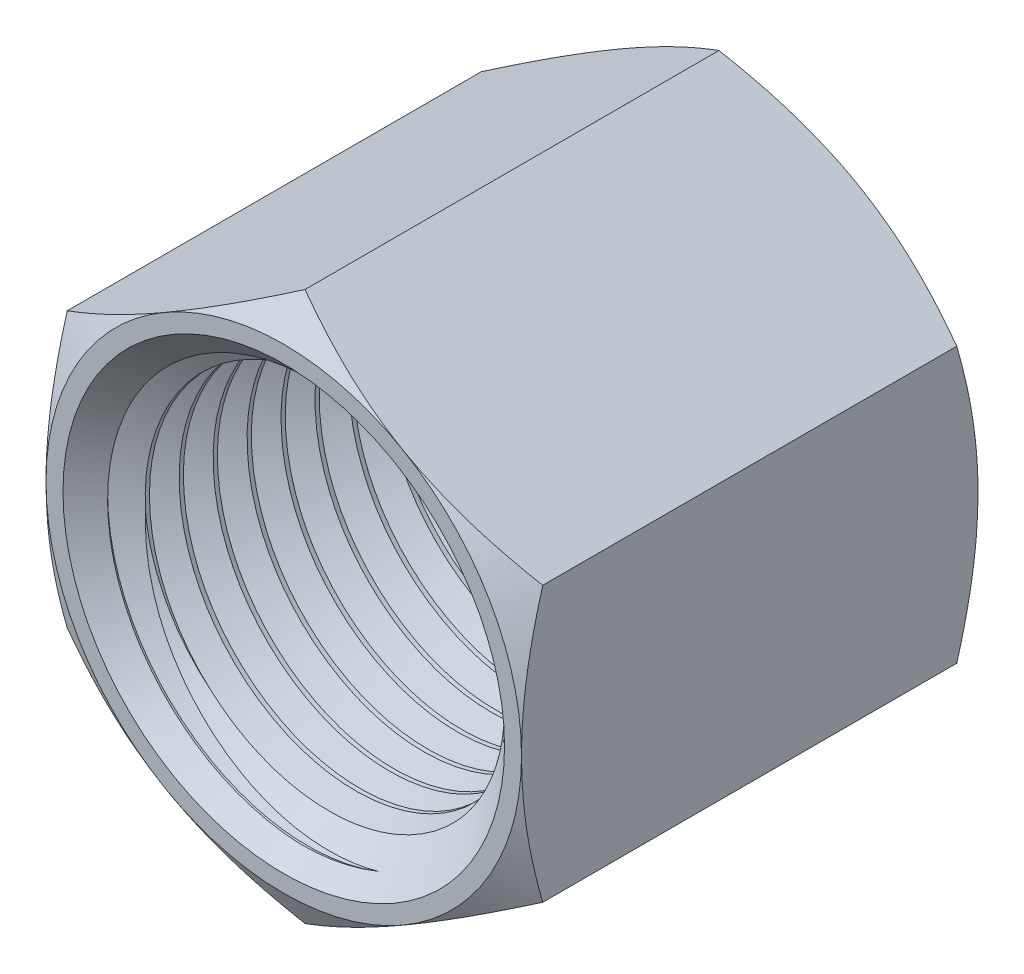
SolidWorks part; units mm, degrees
ref_plane "Front Plane" through (0, 0, 0) normal (0, 0, 1) x (1, 0, 0)
ref_plane "Top Plane" through (0, 0, 0) normal (0, 1, 0) x (1, 0, 0)
ref_plane "Right Plane" through (0, 0, 0) normal (1, 0, 0) x (0, 0, -1)
sketch "Sketch1" plane through (0, 0, 0) normal (1, 0, 0) x (0, 0, -1)
  line L0 (-10.668, 0) -> (10.668, 0) construction
  line L1 (-10.668, 9.525) -> (-10.668, -9.525) construction
  line L2 (0, -11.1125) -> (0, 11.1125) construction
  line L3 (10.668, 7.239) -> (10.668, -7.239) construction
  line L4 (-10.668, 9.525) -> (-12.2555, 9.525) construction
  line L5 (-10.668, 11.1125) -> (10.668, 11.1125) construction
  line L6 (0, 9.525) -> (5.08, 9.525) construction
  line L7 (10.668, -6.35) -> (10.668, 6.35)
  line L10 (-10.668, 9.525) -> (0, 9.525) construction
  line L11 (5.08, 9.525) -> (5.08, 7.239) construction
  line L12 (5.08, 7.239) -> (10.668, 7.239) construction
  line L13 (-10.668, -9.525) -> (0, -9.525) construction
  line L14 (0, -9.525) -> (5.08, -9.525) construction
  line L15 (5.08, -9.525) -> (5.08, -7.239) construction
  line L16 (5.08, -7.239) -> (10.668, -7.239) construction
  point P2 (0, 0)
  point P6 (-10.668, 0)
  point P9 (0, 0)
  point P12 (10.668, 0)
  point P15 (0, 11.1125)
  point P17 (10.668, -7.239)
  point P30 (10.668, 0)
  dimension "Tube" = 14.478
  dimension "Thread Size" = 19.05
  dimension "Hex" = 22.225
  dimension "Length" = 21.336
  dimension "Pitch" = 1.5875
  dimension "Shoulder Length" = 5.588
  dimension "For Tube OD" = 12.7
sketch "Sketch1A" plane through (0, 0, 0) normal (0, 0, 1) x (1, 0, 0)
  line L0 (-7.239, 0) -> (7.239, 0) construction
  line L1 (0, 12.8316) -> (-11.1125, 6.4158) construction
  line L2 (-11.1125, 6.4158) -> (-11.1125, -6.4158) construction
  line L3 (-11.1125, -6.4158) -> (0, -12.8316) construction
  line L4 (0, -12.8316) -> (11.1125, -6.4158) construction
  line L5 (11.1125, -6.4158) -> (11.1125, 6.4158) construction
  line L6 (11.1125, 6.4158) -> (0, 12.8316) construction
  line L7 (0, 7.239) -> (0, -7.239) construction
  line L8 (0, -11.1125) -> (0, 11.1125) construction
  circle A0 centre (0, 0) radius 11.1125 construction
  circle A1 centre (0, 0) radius 6.35
  point P1 (0, 0)
  point P15 (0, -9.525)
ref_plane "Plane1" through (0, 0, 10.668) normal (0, 0, 1) x (1, 0, 0)
sketch "Sketch2" plane through (0, 0, 0) normal (0, 0, 1) x (1, 0, 0)
  line L0 (0, 7.239) -> (0, -7.239) construction
  line L1 (0, 12.8316) -> (-11.1125, 6.4158)
  line L2 (-11.1125, 6.4158) -> (-11.1125, -6.4158)
  line L3 (-11.1125, -6.4158) -> (0, -12.8316)
  line L4 (0, -12.8316) -> (11.1125, -6.4158)
  line L5 (11.1125, -6.4158) -> (11.1125, 6.4158)
  line L6 (11.1125, 6.4158) -> (0, 12.8316)
  circle A0 centre (0, 0) radius 11.1125 construction
  circle A1 centre (0, 0) radius 7.239
extrude "Boss-Extrude1" add sketch "Sketch2" along normal up to vertex (10.668 mm away) and the other way up to vertex (10.668 mm away) up to point (0, 0, 10.668) other way up to point (0, 0, -10.668)
sketch "Sketch3" plane through (0, 0, 0) normal (1, 0, 0) x (0, 0, -1)
  line L0 (-10.668, 9.525) -> (0, 9.525) construction
  line L1 (0, -11.1125) -> (0, 11.1125) construction
  line L2 (0, 9.525) -> (5.08, 9.525) construction
  line L7 (-10.668, 9.525) -> (5.08, 9.525)
  line L8 (5.08, 9.525) -> (5.08, 7.239)
  line L9 (5.08, 7.239) -> (10.668, 7.239)
  line L10 (-10.668, 9.525) -> (-10.668, 0)
  line L11 (-10.668, 0) -> (10.668, 0)
  line L12 (10.668, 0) -> (10.668, 7.239)
revolve "Cut-Revolve1" cut sketch "Sketch3" angle 360 about L11
sketch "Sketch4" plane through (0, 0, 10.668) normal (0, 0, 1) x (1, 0, 0)
  circle A0 centre (0, 0) radius 11.1125
extrude "Cut-Extrude1" cut sketch "Sketch4" against normal blind 2.54 draft 60 flip side to cut
mirror "Mirror1" about plane through (0, 0, 0) normal (0, 0, 1) of "Cut-Extrude1"
sketch "Sketch5" plane through (0, 0, 10.668) normal (0, 0, 1) x (1, 0, 0)
  circle A0 centre (0, 0) radius 10.3187
  dimension "D1" = 20.6375
extrude "Cut-Extrude2" cut sketch "Sketch5" against normal through all draft 45
sketch "Sketch6" plane through (0, 0, 10.668) normal (0, 0, 1) x (1, 0, 0)
  circle A0 centre (0, 0) radius 9.525
curve "Helix/Spiral1" pitch 1.5875 height 17.3355 radius 9.525 centre (0, 0, 10.668) axis (0, 0, -1) start towards (0, 1, 0)
sketch "Sketch7" plane through (0, 0, 10.668) normal (0, 0, 1) x (1, 0, 0)
  circle A0 centre (0, 0) radius 10.3187 construction
  circle A1 centre (0, 0) radius 10.3187
extrude "Boss-Extrude2" add sketch "Sketch7" against normal up to surface (15.748 mm away) up to face at (0, -9.525, -5.08)
sketch "Sketch8" plane through (0, 0, 10.668) normal (0, 0, 1) x (1, 0, 0)
  circle A0 centre (0, 0) radius 9.525
  dimension "D1" = 19.05
extrude "Boss-Extrude3" add sketch "Sketch8" against normal up to vertex (15.748 mm away) separate body up to point (0, 9.525, -5.08)
sketch "Sketch9" plane through (0, 0, 0) normal (1, 0, 0) x (0, 0, -1)
  line L0 (-12.2059, 9.6109) -> (-10.6184, 9.6109) construction
  line L1 (-10.6184, 9.6109) -> (-11.4121, 8.2361) construction
  line L2 (-11.4121, 8.2361) -> (-12.2059, 9.6109) construction
  line L3 (-11.4121, 8.2361) -> (-11.4121, 8.408) construction
  line L4 (-11.4121, 8.408) -> (-11.4121, 9.4391) construction
  line L5 (-11.4121, 9.4391) -> (-11.4121, 9.6109) construction
  line L6 (-11.5114, 8.408) -> (-11.3129, 8.408) construction
  line L7 (-10.668, 9.525) -> (-11.3129, 8.408)
  line L8 (-10.7176, 9.4391) -> (-12.1067, 9.4391) construction
  line L9 (-11.3129, 8.408) -> (-11.5114, 8.408)
  line L10 (-10.668, 9.525) -> (-12.1563, 9.525) construction
  line L11 (-11.5114, 8.408) -> (-12.1563, 9.525)
  line L12 (-12.1563, 9.525) -> (-10.668, 9.525)
  point P12 (-11.4121, 8.408)
  point P14 (-11.4121, 9.4391)
  point P15 (-11.4121, 9.525)
  point P16 (-11.4121, 9.525)
  dimension "D2" = 0.1984
sweep "Cut-Sweep1" cut profiles "Sketch9" path "Helix/Spiral1" align with end faces yes
combine bodies "Combine1" operation type subtract main body 111 bodies to subtract 113
sketch "Sketch10" plane through (0, 0, 10.668) normal (0, 0, 1) x (1, 0, 0)
  circle A2 centre (0, 0) radius 10.3187
  circle A3 centre (0, 0) radius 10.3187
  dimension "D1" = 0
extrude "Cut-Extrude3" cut sketch "Sketch10" against normal through all draft 45
equation "\"D3@Helix/Spiral1\"=(\"Length@Sketch1\" - \"Shoulder Length@Sketch1\") + \"Pitch@Sketch1\""
equation "\"D4@Helix/Spiral1\"=\"Pitch@Sketch1\""
equation "\"D1@Sketch9\" = \"Pitch@Sketch1\""
equation "\"D2@Sketch9\" = \"D1@Sketch9\" / 8"
equation "\"D1@Sketch5\" = \"Thread Size@Sketch1\" + \"Pitch@Sketch1\""
equation "\"D1@Sketch8\" = \"Thread Size@Sketch1\""
